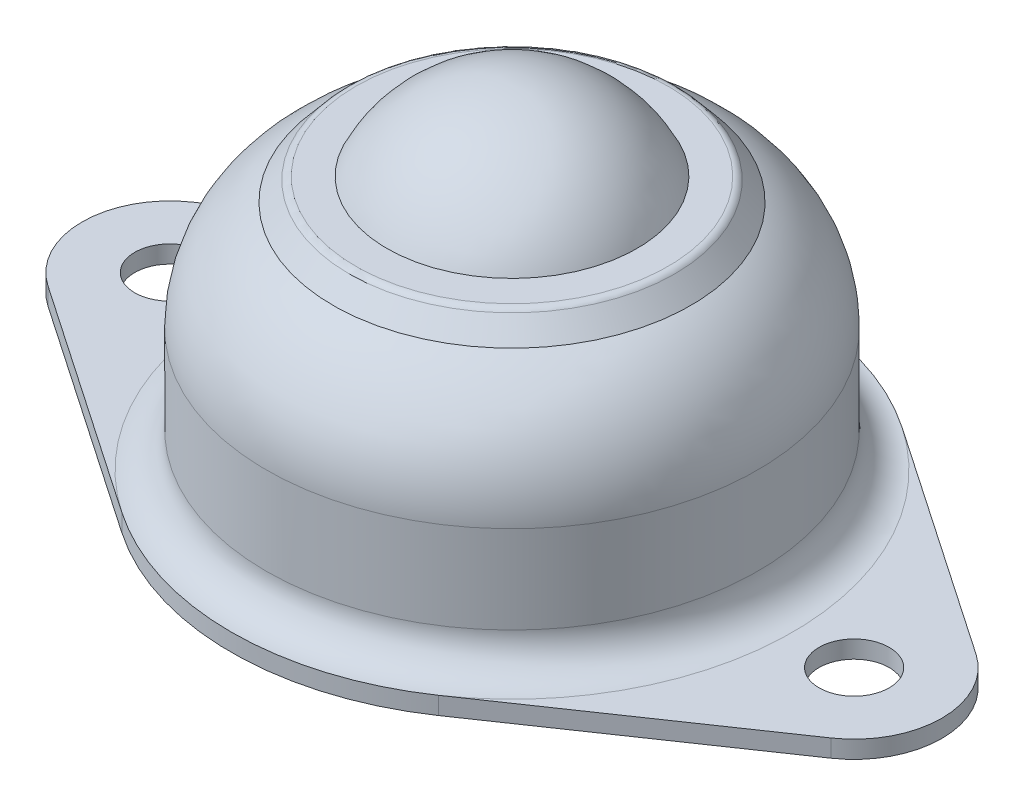
SolidWorks part; units mm, degrees
ref_plane "Front" through (0, 0, 0) normal (0, 0, 1) x (1, 0, 0)
ref_plane "Top" through (0, 0, 0) normal (0, 1, 0) x (1, 0, 0)
ref_plane "Right" through (0, 0, 0) normal (1, 0, 0) x (0, 0, -1)
sketch "草圖1" plane through (0, 0, 0) normal (0, 1, 0) x (1, 0, 0)
  line L0 (-19.5, 0) -> (19.5, 0) construction
  line L1 (-22.3205, 4.1285) -> (-9.0256, 13.2113)
  line L2 (9.0256, 13.2113) -> (22.3205, 4.1285)
  line L3 (-22.3205, -4.1285) -> (-9.0256, -13.2113)
  line L4 (9.0256, -13.2113) -> (22.3205, -4.1285)
  circle A0 centre (19.5, 0) radius 2
  circle A1 centre (-19.5, 0) radius 2
  arc A3 (-22.3205, 4.1285) -> (-22.3205, -4.1285) centre (-19.5, 0) ccw
  arc A4 (22.3205, -4.1285) -> (22.3205, 4.1285) centre (19.5, 0) ccw
  arc A5 (-9.0256, -13.2113) -> (9.0256, -13.2113) centre (0, 0) ccw
  arc A8 (9.0256, 13.2113) -> (-9.0256, 13.2113) centre (0, 0) ccw
  dimension "D1" = 4
  dimension "D2" = 4
  dimension "D4" = 16
  dimension "D5" = 10
  dimension "D6" = 10
  dimension "D7" = 16
  dimension "D3" = 39
extrude "填料-伸長1" add sketch "草圖1" along normal blind 1
sketch "草圖2" plane through (0, 0, 0) normal (0, 0, 1) x (1, 0, 0)
  line L0 (-14, 1) -> (-14, 8)
  line L1 (-22.3205, 1) -> (-9.0256, 1) construction
  line L3 (0, 20) -> (0, 1)
  line L4 (9.0256, 1) -> (-9.0256, 1) construction
  line L5 (0, 1) -> (-14, 1)
  line L6 (-7.1309, 15.5) -> (-8.8978, 15.5)
  line L7 (-9.2808, 15.3214) -> (-10.2002, 14.2256)
  arc A1 (-7.1309, 15.5) -> (0, 20) centre (0, 12.1) cw
  arc A3 (-14, 8) -> (-10.2002, 14.2256) centre (-7, 8) cw
  arc A4 (-8.8978, 15.5) -> (-9.2808, 15.3214) centre (-8.8978, 15) ccw
  point P14 (-9.1309, 15.5)
  dimension "D1" = 7.9
  dimension "D4" = 4.5
  dimension "D5" = 7
  dimension "D7" = 130
  dimension "D8" = 7
  dimension "D9" = 0.5
  dimension "D2" = 19
  dimension "D3" = 14
  dimension "D6" = 2
  dimension "D10" = 11.1
revolve "旋轉1" add sketch "草圖2" angle 360 about L3
fillet "圓角1" radius 2 1 edges at (0, 1, 14)
sketch "草圖3" plane through (0, 0, 0) normal (0, 0, 1) x (1, 0, 0)
  line L3 (0, 0) -> (-13, 0)
  line L6 (-22.3205, 0) -> (-9.0256, 0) construction
  line L7 (-13, 0) -> (-13, 7)
  line L11 (-13, 7) -> (-12.7, 7)
  line L13 (-9.0256, 1) -> (9.0256, 1) construction
  line L14 (0, 1) -> (0, 0)
  spline S0 degree 2 poles (-12.7, 7) (-8.5987, 1) (0, 1) knots 0 0 0 1 1 1
  dimension "D2" = 13
  dimension "D3" = 7
  dimension "D4" = 0.3
revolve "除料-旋轉1" cut sketch "草圖3" angle 360 about L14
fillet "圓角3" radius 2 1 edges at (-13, 0, 0)
